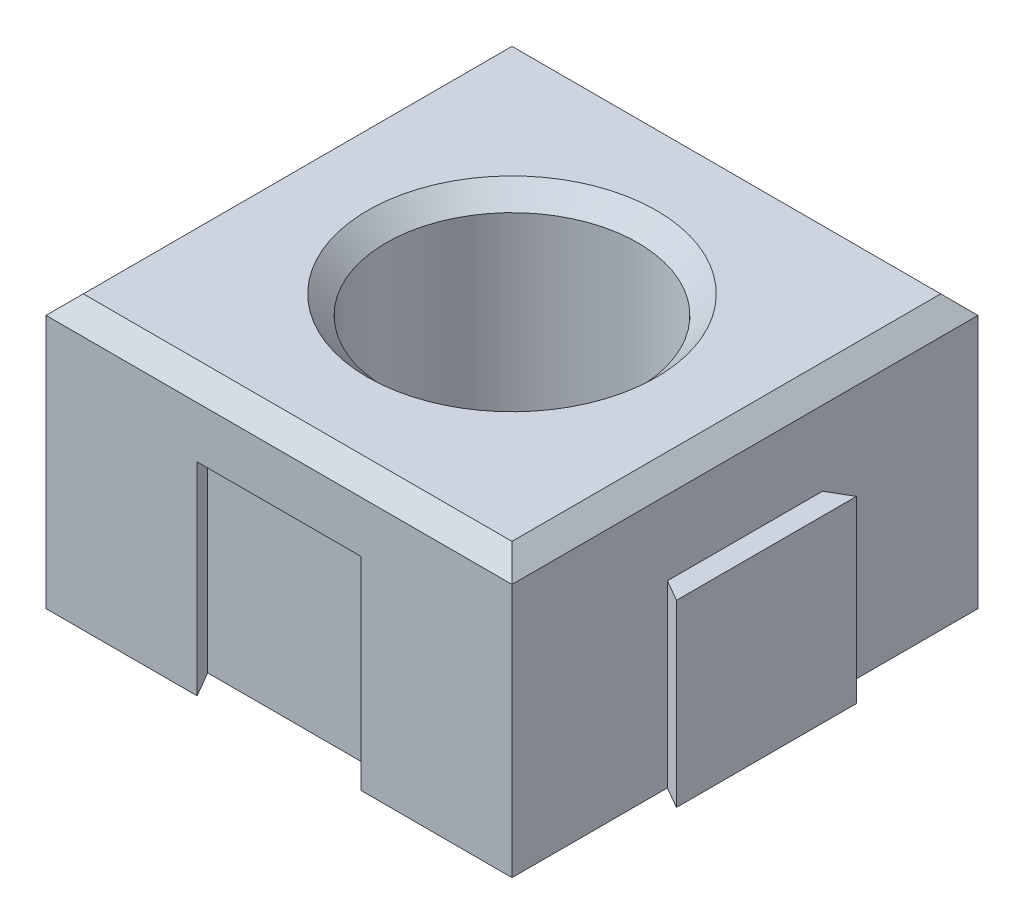
SolidWorks part; units mm, degrees
ref_plane "Left Plane" through (0, 0, 0) normal (0, 0, 1) x (1, 0, 0)
ref_plane "Bottom Plane" through (0, 0, 0) normal (0, 1, 0) x (1, 0, 0)
ref_plane "Back Plane" through (0, 0, 0) normal (1, 0, 0) x (0, 0, -1)
sketch "Sketch1" plane through (0, 0, 0) normal (0, 1, 0) x (1, 0, 0)
  line L1 (0, 0) -> (50, 0)
  line L2 (0, 0) -> (0, 50)
  line L3 (0, 50) -> (50, 50)
  line L4 (50, 0) -> (50, 50)
  dimension "D1" = 50
extrude "Boss-Extrude1" add sketch "Sketch1" along normal blind 30
sketch "Sketch2" plane through (0, 30, 0) normal (0, 1, 0) x (1, 0, 0)
  line L0 (0, 0) -> (50, 50) construction
  line L1 (0, 50) -> (50, 0) construction
  circle A0 centre (25, 25) radius 13.5
  dimension "D1" = 27
extrude "Cut-Extrude1" cut sketch "Sketch2" against normal blind 26
sketch "Sketch3" plane through (0, 0, 0) normal (0, 1, 0) x (1, 0, 0)
  line L0 (50, 33.5566) -> (52.5, 35) construction
  line L1 (50, 0) -> (50, 50) construction
  line L2 (52.5, 35) -> (52.5, 15) construction
  line L3 (52.5, 15) -> (50, 16.4434) construction
  line L4 (50, 25) -> (52.5, 25) construction
  line L5 (16.4434, 50) -> (15, 52.5) construction
  line L6 (50, 50) -> (0, 50) construction
  line L7 (15, 52.5) -> (35, 52.5) construction
  line L8 (35, 52.5) -> (33.5566, 50) construction
  line L9 (25, 52.5) -> (25, 50) construction
  line L10 (0, 33.5566) -> (2.5, 35) construction
  line L11 (0, 50) -> (0, 0) construction
  line L12 (2.5, 35) -> (2.5, 15) construction
  line L13 (2.5, 15) -> (0, 16.4434) construction
  line L14 (0, 25) -> (2.5, 25) construction
  line L15 (16.4434, 0) -> (15, 2.5) construction
  line L16 (0, 0) -> (50, 0) construction
  line L17 (15, 2.5) -> (35, 2.5) construction
  line L18 (35, 2.5) -> (33.5566, 0) construction
  line L19 (25, 0) -> (25, 2.5) construction
  line L20 (50, 16.6743) -> (50, 33.3257)
  line L21 (33.3257, 50) -> (16.6743, 50)
  line L23 (16.4434, 0) -> (33.5566, 0) construction
  line L24 (50, 33.3257) -> (52.3, 34.6536)
  line L25 (52.3, 34.6536) -> (52.3, 15.3464)
  line L26 (52.3, 15.3464) -> (50, 16.6743)
  line L27 (52.3, 34.6536) -> (52.2, 34.8268) construction
  line L28 (16.2124, 0) -> (14.6536, 2.7)
  line L29 (52.3, 34.6536) -> (52.5, 34.6536) construction
  line L30 (14.6536, 2.7) -> (35.3464, 2.7)
  line L31 (35.3464, 2.7) -> (33.7876, 0)
  line L32 (33.7876, 0) -> (16.2124, 0)
  line L33 (35, 2.5) -> (35, 2.7) construction
  line L34 (35, 2.5) -> (35.1732, 2.4) construction
  line L35 (0, 33.7876) -> (2.7, 35.3464)
  line L36 (2.7, 35.3464) -> (2.7, 14.6536)
  line L37 (2.7, 14.6536) -> (0, 16.2124)
  line L38 (0, 16.2124) -> (0, 33.7876)
  line L39 (2.4, 14.8268) -> (2.5, 15) construction
  line L40 (2.5, 15) -> (2.7, 15) construction
  line L41 (16.6743, 50) -> (15.3464, 52.3)
  line L42 (15.3464, 52.3) -> (34.6536, 52.3)
  line L43 (34.6536, 52.3) -> (33.3257, 50)
  line L44 (15.3464, 52.5) -> (15.3464, 52.3) construction
  line L45 (15.1732, 52.2) -> (15.3464, 52.3) construction
  point P8 (50, 25)
  point P39 (52.3, 25)
  point P40 (25, 0)
  point P53 (0, 25)
  point P59 (25, 52.3)
  point P63 (25, 50)
  dimension "D1" = 0.2
  dimension "D2" = 60
  dimension "D3" = 2.5
  dimension "D4" = 20
extrude "Boss-Extrude2" add sketch "Sketch3" along normal blind 20 contours L20 L24 L25 L26
extrude "Boss-Extrude3" add sketch "Sketch3<3>" along normal blind 20 contours L21 L41 L42 L43
sketch "Sketch3<3>" plane through (0, 0, 0) normal (0, 1, 0) x (1, 0, 0) same geometry as "Sketch3"
extrude "Cut-Extrude5" cut sketch "Sketch3<6>" along normal blind 20 contours L38 L35 L36 L37
sketch "Sketch3<6>" plane through (0, 0, 0) normal (0, 1, 0) x (1, 0, 0) same geometry as "Sketch3"
extrude "Cut-Extrude6" cut sketch "Sketch3<7>" along normal blind 20 contours L32 L28 L30 L31
sketch "Sketch3<7>" plane through (0, 0, 0) normal (0, 1, 0) x (1, 0, 0) same geometry as "Sketch3"
chamfer "Chamfer1" distance 2 angle 45 5 edges at (25, 30, -50) (50, 30, -25) (25, 30, 0) (0, 30, -25) (25, 30, -11.5)
sketch "Sketch4" plane through (0, 0, 0) normal (0, 1, 0) x (1, 0, 0)
  line L0 (12.5, 12.5) -> (37.5, 37.5) construction
  line L1 (12.5, 12.5) -> (37.5, 12.5) construction
  line L2 (12.5, 12.5) -> (12.5, 37.5) construction
  line L3 (12.5, 37.5) -> (37.5, 37.5) construction
  line L4 (37.5, 12.5) -> (37.5, 37.5) construction
  line L5 (12.5, 37.5) -> (37.5, 12.5) construction
  line L6 (0, 0) -> (12.5, 12.5) construction
  line L7 (12.5, 37.5) -> (0, 50) construction
  line L8 (50, 50) -> (37.5, 37.5) construction
  line L9 (50, 0) -> (37.5, 12.5) construction
  line L10 (0, 25) -> (25, 25) construction
  circle A0 centre (12.5, 37.5) radius 3.1
  circle A1 centre (37.5, 37.5) radius 3.1
  circle A2 centre (37.5, 12.5) radius 3.1
  circle A3 centre (12.5, 12.5) radius 3.1
  point P15 (12.5, 25)
  dimension "D1" = 6.2
extrude "Cut-Extrude4" cut sketch "Sketch4" along normal blind 4
chamfer "Chamfer2" distance 1 angle 45 4 edges at (37.5, 4, -9.4) (12.5, 4, -9.4) (12.5, 4, -34.4) (37.5, 4, -34.4)
chamfer "Chamfer3" distance 0.75 angle 45 24 edges at (41.8938, 0, 0) (50, 0, -8.3372) (50, 0, -41.6628) (41.6628, 0, -50) (8.3372, 0, -50) (0, 0, -41.8938) (0, 0, -8.1062) (8.1062, 0, 0) (12.5, 0, -34.4) (37.5, 0, -34.4) (37.5, 0, -9.4) (12.5, 0, -9.4) (51.15, 0, -16.0104) (52.3, 0, -25) (51.15, 0, -33.9896) (33.9896, 0, -51.15) (25, 0, -52.3) (16.0104, 0, -51.15) (1.35, 0, -34.567) (2.7, 0, -25) (1.35, 0, -15.433) (15.433, 0, -1.35) (25, 0, -2.7) (34.567, 0, -1.35)
chamfer "Chamfer4" distance 2.5 angle 45 2 edges at (25, 20, 0) (0, 20, -25)
